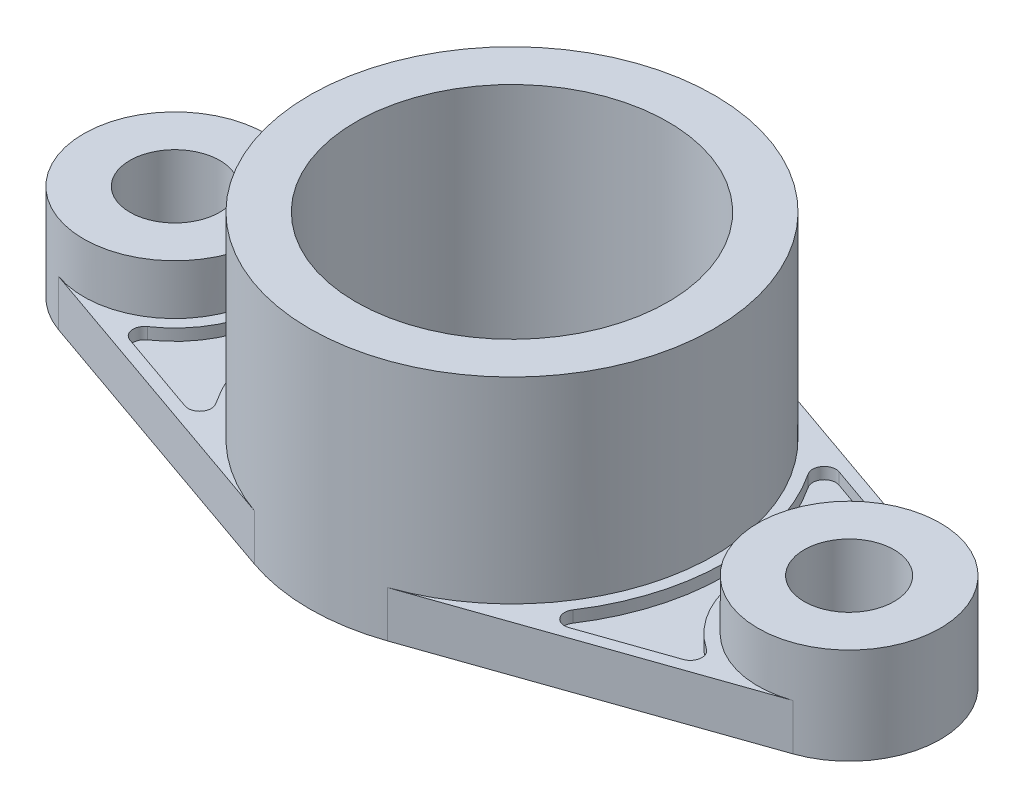
SolidWorks part; units mm, degrees
ref_plane "Front Plane" through (0, 0, 0) normal (0, 0, 1) x (1, 0, 0)
ref_plane "Top Plane" through (0, 0, 0) normal (0, 1, 0) x (1, 0, 0)
ref_plane "Right Plane" through (0, 0, 0) normal (1, 0, 0) x (0, 0, -1)
sketch "Sketch2" plane through (0, 0, 0) normal (0, 1, 0) x (1, 0, 0)
  line L0 (-87.5, 0) -> (87.5, 0) construction
  line L1 (0, 0) -> (0, 24.843)
  line L2 (-95.2986, 22.3431) -> (-17.301, 49.5674)
  line L3 (-95.2986, -22.3431) -> (-17.301, -49.5674)
  line L4 (95.2986, -22.3431) -> (17.301, -49.5674)
  line L5 (95.2986, 22.3431) -> (17.301, 49.5674)
  circle A0 centre (0, 0) radius 52.5
  circle A1 centre (0, 0) radius 40.5
  circle A2 centre (-87.5, 0) radius 11.665
  circle A3 centre (-87.5, 0) radius 23.665
  circle A4 centre (87.5, 0) radius 11.665
  circle A5 centre (87.5, 0) radius 23.665
  point P8 (0, 0)
  point P14 (0, 0)
  dimension "D1" = 105
  dimension "D3" = 12
  dimension "D4" = 23.33
  dimension "D2" = 12
extrude "Boss-Extrude5" add sketch "Sketch2" along normal blind 63 contours A0 L0 A1 | L0 A0 A1 region at (-41.8479, 0, -29.7172) region at (-46.5, 0, 1.1739)
extrude "Boss-Extrude6" add sketch "Sketch2<3>" along normal blind 25 separate body contours A2 A3 | A5 A4 region at (-74.1858, 0, -18.7492) region at (106.2492, 0, -13.3142)
sketch "Sketch2<3>" plane through (0, 0, 0) normal (0, 1, 0) x (1, 0, 0) same geometry as "Sketch2"
extrude "Boss-Extrude7" add sketch "Sketch2<4>" along normal blind 12 contours L0 A3 L3 A0 | L0 A0 L4 A5 | A0 L0 A5 L5 | A3 L0 A0 L2 region at (-58.0855, 0, -23.124) region at (-58.0855, 0, 23.124) region at (58.0855, 0, -23.124) region at (58.0855, 0, 23.124)
sketch "Sketch2<4>" plane through (0, 0, 0) normal (0, 1, 0) x (1, 0, 0) same geometry as "Sketch2"
sketch "Sketch6" plane through (0, 12, 0) normal (0, 1, 0) x (1, 0, 0)
  line L0 (-49.826, 35.0373) -> (-71.8093, 27.3643)
  line L1 (-71.8093, -27.3643) -> (-49.826, -35.0373)
  line L2 (-17.301, 49.5674) -> (-95.2986, 22.3431)
  line L3 (-95.2986, -22.3431) -> (-17.301, -49.5674)
  line L4 (-17.301, 49.5674) -> (-95.2986, 22.3431)
  line L5 (-95.2986, -22.3431) -> (-17.301, -49.5674)
  line L6 (-78.3996, -25.064) -> (-40.0101, -38.4635) construction
  line L7 (-40.0101, 38.4635) -> (-78.3996, 25.064) construction
  arc A0 (-72.5075, -22.051) -> (-72.5075, 22.051) centre (-87.5, 0) ccw
  arc A1 (-46.3329, 30.5534) -> (-46.3329, -30.5534) centre (0, 0) ccw
  arc A2 (-17.301, 49.5674) -> (-17.301, -49.5674) centre (0, 0) ccw
  arc A3 (-95.2986, -22.3431) -> (-95.2986, 22.3431) centre (-87.5, 0) ccw
  arc A4 (-17.301, 49.5674) -> (-17.301, -49.5674) centre (0, 0) ccw
  arc A5 (-95.2986, -22.3431) -> (-95.2986, 22.3431) centre (-87.5, 0) ccw
  arc A6 (-40.0101, 38.4635) -> (-40.0101, -38.4635) centre (0, 0) ccw construction
  arc A7 (-49.826, -35.0373) -> (-46.3329, -30.5534) centre (-48.8374, -32.2049) ccw
  arc A8 (-78.3996, -25.064) -> (-78.3996, 25.064) centre (-87.5, 0) ccw construction
  arc A9 (-71.8093, -27.3643) -> (-72.5075, -22.051) centre (-70.8207, -24.5319) cw
  arc A10 (-46.3329, 30.5534) -> (-49.826, 35.0373) centre (-48.8374, 32.2049) ccw
  arc A11 (-72.5075, 22.051) -> (-71.8093, 27.3643) centre (-70.8207, 24.5319) cw
  point P34 (0, 0)
  dimension "D3" = 3
  dimension "D1" = 0
  dimension "D2" = 3
extrude "Cut-Extrude2" cut sketch "Sketch6" against normal blind 3 contours L0 A11 A0 A9 L1 A7 A1 A10
mirror "Mirror1" about plane through (0, 0, 0) normal (1, 0, 0) of "Cut-Extrude2"
